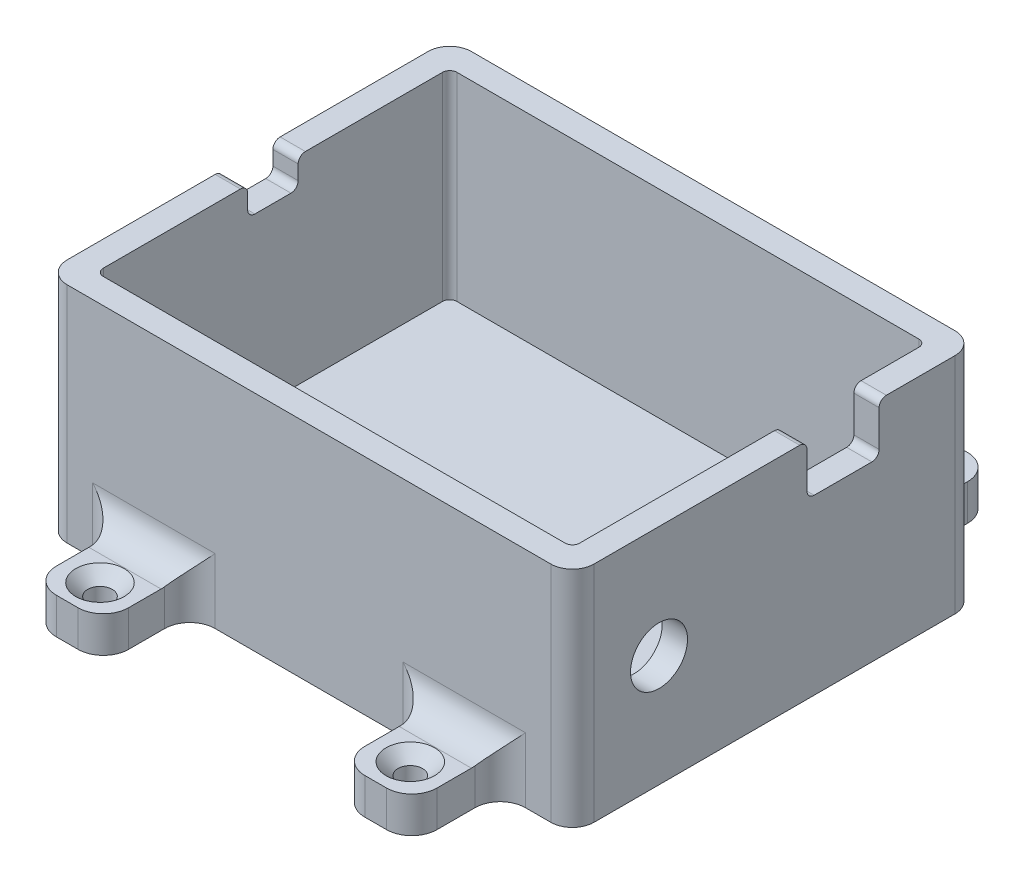
SolidWorks part; units mm, degrees
ref_plane "Plano frontal" through (0, 0, 0) normal (0, 0, 1) x (1, 0, 0)
ref_plane "Plano superior" through (0, 0, 0) normal (0, 1, 0) x (1, 0, 0)
ref_plane "Plano direito" through (0, 0, 0) normal (1, 0, 0) x (0, 0, -1)
sketch "Esboço1" plane through (0, 0, 0) normal (0, 1, 0) x (1, 0, 0)
  line L0 (-36.5, 28) -> (36.5, 28)
  line L1 (-32.5, 24) -> (32.5, 24) construction
  line L2 (-32.5, 24) -> (-32.5, -24) construction
  line L3 (-32.5, -24) -> (32.5, -24) construction
  line L4 (32.5, 24) -> (32.5, -24) construction
  line L5 (-32.5, 24) -> (32.5, -24) construction
  line L6 (-32.5, -24) -> (32.5, 24) construction
  line L7 (36.5, 28) -> (36.5, -28)
  line L8 (-36.5, -28) -> (36.5, -28)
  line L9 (-36.5, 28) -> (-36.5, -28)
  point P0 (0, 0)
  dimension "D1" = 48
  dimension "D3" = 65
  dimension "D2" = 4
extrude "Ressalto-extrusão1" add sketch "Esboço1" along normal blind 31
shell "Casca1" thickness 3.5 removed face at (0, 31, 0)
sketch "Esboço2" plane through (0, 31, 0) normal (0, 1, 0) x (1, 0, 0)
  line L0 (33, -24.5) -> (33, 24.5) construction
  line L1 (33, 14.5) -> (36.5, 14.5)
  line L2 (33, 14.5) -> (33, 4.5)
  line L3 (33, 4.5) -> (36.5, 4.5)
  line L4 (36.5, 14.5) -> (36.5, 4.5)
  line L5 (36.5, -28) -> (36.5, 28) construction
  line L6 (33, 24.5) -> (-33, 24.5) construction
  dimension "D1" = 10
  dimension "D2" = 10
extrude "Ressalto-extrusão2" add sketch "Esboço2" against normal blind 5
extrude "Corte-extrusão1" cut sketch "Esboço2<2>" against normal blind 7
sketch "Esboço2<2>" plane through (0, 31, 0) normal (0, 1, 0) x (1, 0, 0) same geometry as "Esboço2"
sketch "Esboço4" plane through (0, 31, 0) normal (0, 1, 0) x (1, 0, 0)
  line L0 (-36.5, 28) -> (-36.5, -28) construction
  line L1 (-36.5, 3.5) -> (-33, 3.5)
  line L2 (-36.5, 3.5) -> (-36.5, -3.5)
  line L3 (-36.5, -3.5) -> (-33, -3.5)
  line L4 (-33, 3.5) -> (-33, -3.5)
  line L5 (-33, 24.5) -> (-33, -24.5) construction
  point P8 (-33, 0)
  point P9 (-33, 0)
  dimension "D1" = 7
extrude "Corte-extrusão2" cut sketch "Esboço4" against normal blind 4
sketch "Esboço5" plane through (36.5, 0, 0) normal (1, 0, 0) x (0, 0, -1)
  line L1 (-28, 31) -> (-28, 0) construction
  circle A0 centre (-16, 15.5) radius 3.95
  point P6 (-28, 15.5)
  dimension "D2" = 7.9
  dimension "D1" = 12
extrude "Corte-extrusão3" cut sketch "Esboço5" against normal up to next
fillet "Filete1" radius 3 4 edges at (36.5, 15.5, -28) (-36.5, 15.5, -28) (-36.5, 15.5, 28) (36.5, 15.5, 28)
sketch "Esboço6" plane through (0, 0, 0) normal (0, 1, 0) x (1, 0, 0)
  line L0 (-33.5, -28) -> (33.5, -28) construction
  line L1 (16.5, -28) -> (26.5, -28)
  line L2 (16.5, -28) -> (16.5, -40.2603)
  line L3 (16.5, -40.2603) -> (26.5, -40.2603)
  line L4 (26.5, -28) -> (26.5, -40.2603)
  line L5 (36.5, -25) -> (36.5, 25) construction
  line L6 (-26.5, -28) -> (-16.5, -28)
  line L7 (-26.5, -28) -> (-26.5, -40)
  line L8 (-26.5, -40) -> (-16.5, -40)
  line L9 (-16.5, -28) -> (-16.5, -40)
  dimension "D1" = 12
  dimension "D2" = 10
  dimension "D3" = 10
  dimension "D4" = 10
extrude "Ressalto-extrusão3" add sketch "Esboço6" along normal blind 5
hole_wizard "Escareado para SFHCS M31" positions "Esboço7" profile "Esboço8" countersink size "M3" standard "Ansi Metric" end condition up to next
sketch "Esboço7" plane through (0, 5, 0) normal (0, 1, 0) x (1, 0, 0)
  line L0 (-26.5, -40) -> (-16.5, -40) construction
  line L1 (16.5, -40.2603) -> (26.5, -40.2603) construction
  point P0 (-21.5, -35.4603)
  point P2 (21.5, -35.4603)
  point P7 (-21.5, -40)
  point P11 (21.5, -40.2603)
  dimension "D1" = 4.8
sketch "Esboço8" plane through (-21.5, 5, 35.4603) normal (1, 0, 0) x (0, 0, 1)
  line L0 (0, 0) -> (0, 5)
  line L1 (0, 5) -> (1.7, 5)
  line L2 (1.7, 5) -> (1.7, 1.66)
  line L3 (1.7, 1.66) -> (3.36, 0)
  line L5 (3.36, 0) -> (0, 0)
  line L6 (-1.7, 1.66) -> (-3.36, 0) construction
  line L11 (0, -6.35) -> (0, 107.95) construction
  dimension "Thru Hole Dia." = 3.4
  dimension "Thru Hole Depth" = 5
  dimension "Near C'Sink Dia." = 6.72
  dimension "Near C'Sink Angle" = 90
mirror "Espelhar9" about plane through (0, 0, 0) normal (0, 0, 1) of "Escareado para SFHCS M31", "Ressalto-extrusão3"
fillet "Filete4" radius 3.5 16 edges at (-26.5, 2.5, -28) (-26.5, 2.5, -40) (-16.5, 2.5, -40) (-16.5, 2.5, -28) (16.5, 2.5, -28) (16.5, 2.5, -40.2603) (26.5, 2.5, -40.2603) (26.5, 2.5, -28) (-26.5, 2.5, 28) (16.5, 2.5, 28) (26.5, 2.5, 28) (26.5, 2.5, 40.2603) (16.5, 2.5, 40.2603) (-16.5, 2.5, 28) (-26.5, 2.5, 40) (-16.5, 2.5, 40)
fillet "Filete5" radius 4 4 edges at (-21.5, 5, -28) (21.5, 5, -28) (21.5, 5, 28) (-21.5, 5, 28)
fillet "Filete6" radius 1 12 edges at (-34.75, 27, 3.5) (-34.75, 27, -3.5) (34.75, 24, -14.5) (34.75, 24, -4.5) (34.75, 31, -4.5) (34.75, 31, -14.5) (-34.75, 31, 3.5) (-34.75, 31, -3.5) (33, 17.25, 24.5) (33, 17.25, -24.5) (-33, 17.25, 24.5) (-33, 17.25, -24.5)
